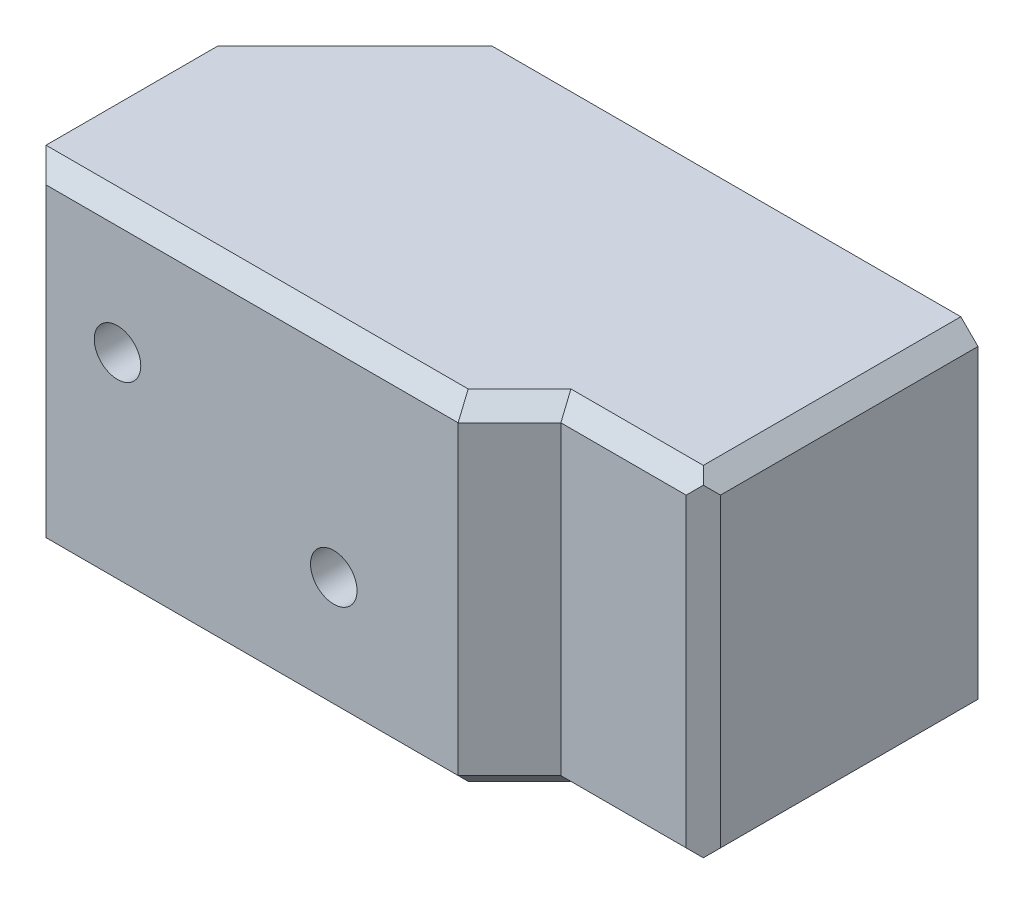
SolidWorks part; units mm, degrees
material "PET"
ref_plane "Front Plane" through (0, 0, 0) normal (0, 0, 1) x (1, 0, 0)
ref_plane "Top Plane" through (0, 0, 0) normal (0, 1, 0) x (1, 0, 0)
ref_plane "Right Plane" through (0, 0, 0) normal (1, 0, 0) x (0, 0, -1)
sketch "Sketch1" plane through (0, 0, 0) normal (0, 0, 1) x (1, 0, 0)
  line L0 (37.2, 18.6106) -> (1.8, 18.6106) construction
  line L1 (1.8, -1.3894) -> (56.25, -1.3894)
  line L2 (1.8, -1.3894) -> (1.8, 18.6106)
  line L3 (1.8, 18.6106) -> (56.25, 18.6106)
  line L4 (56.25, -1.3894) -> (56.25, 18.6106)
  line L5 (37.2, 18.6106) -> (37.2, -1.3894) construction
  point P5 (1.8, 18.6106)
  dimension "D1" = 19.05
extrude "Boss-Extrude1" add sketch "Sketch1" along normal blind 3.175
sketch "Sketch2" plane through (56.25, 0, 0) normal (1, 0, 0) x (0, 0, -1)
  line L0 (0, 18.6106) -> (0, 21.1506)
  line L1 (0, 21.1506) -> (22.225, 21.1506)
  line L6 (0, 8.6106) -> (-3.175, 8.6106) construction
  line L7 (0, -1.3894) -> (0, 18.6106) construction
  line L8 (-3.175, -1.3894) -> (-3.175, 18.6106) construction
  line L9 (-3.175, 18.6106) -> (-3.175, 24.3256)
  line L10 (-3.175, 24.3256) -> (22.225, 24.3256)
  line L11 (0, 18.6106) -> (-3.175, 18.6106)
  line L12 (22.225, 21.1506) -> (22.225, 24.3256)
  line L13 (22.225, -3.9294) -> (22.225, -7.1044)
  line L14 (0, -1.3894) -> (-3.175, -1.3894)
  line L15 (-3.175, -7.1044) -> (22.225, -7.1044)
  line L16 (-3.175, -1.3894) -> (-3.175, -7.1044)
  line L17 (0, -3.9294) -> (22.225, -3.9294)
  line L18 (0, -1.3894) -> (0, -3.9294)
  dimension "D1" = 22.225
  dimension "D2" = 2.54
  dimension "D3" = 3.175
extrude "Boss-Extrude2" add sketch "Sketch2" against normal up to surface (54.45 mm away) up to face at (1.8, 8.6106, 1.5875)
sketch "Sketch3" plane through (56.25, 0, 0) normal (1, 0, 0) x (0, 0, -1)
  line L1 (-3.175, 24.3256) -> (22.225, 24.3256)
  line L2 (-3.175, 24.3256) -> (-3.175, -7.1044)
  line L3 (-3.175, -7.1044) -> (22.225, -7.1044)
  line L4 (22.225, 24.3256) -> (22.225, -7.1044)
extrude "Boss-Extrude3" add sketch "Sketch3" along normal blind 3.175
chamfer "Chamfer1" distance 1.5875 angle 45 8 edges at (59.425, 24.3256, -9.525) (59.425, 8.6106, 3.175) (59.425, -7.1044, -9.525) (29.025, 21.1506, 0) (29.025, -3.9294, 0) (56.25, 21.1506, -11.1125) (56.25, 8.6106, 0) (56.25, -3.9294, -11.1125)
chamfer "Chamfer2" distance 12.7 angle 45 2 edges at (1.8, 22.7381, -22.225) (1.8, -5.5169, -22.225)
sketch "Sketch5" plane through (0, 0, 3.175) normal (0, 0, 1) x (1, 0, 0)
  line L0 (1.8, -7.1044) -> (57.8375, -7.1044) construction
  line L1 (1.8, 24.3256) -> (33.55, 24.3256)
  line L2 (1.8, 24.3256) -> (1.8, -7.1044)
  line L3 (1.8, -7.1044) -> (33.55, -7.1044)
  line L4 (33.55, 24.3256) -> (33.55, -7.1044)
  dimension "D1" = 31.75
extrude "Boss-Extrude5" add sketch "Sketch5" along normal offset from surface (4.7498 mm away) 7.9248 up to face at (28.2313, 8.6106, 0)
chamfer "Chamfer3" distance 12.7 angle 45 1 edges at (33.55, 8.6106, 3.175)
chamfer "Chamfer4" distance 1.5875 angle 45 7 edges at (52.0438, -7.1044, 3.175) (43.8751, -7.1044, 5.5499) (21.6501, -7.1044, 7.9248) (1.8, 8.6106, 7.9248) (21.6501, 24.3256, 7.9248) (43.8751, 24.3256, 5.5499) (52.0438, 24.3256, 3.175)
hole_wizard "#6 Clearance Hole1" positions "Sketch6" profile "Sketch7" hole size "#6" standard "ANSI Inch" end condition up to next
sketch "Sketch6" plane through (0, 0, 7.9248) normal (0, 0, 1) x (1, 0, 0)
  point P1 (10, 12.6106)
  point P4 (30, 4.6106)
sketch "Sketch7" plane through (10, 12.6106, 7.9248) normal (1, 0, 0) x (0, -1, 0)
  line L0 (0, 0) -> (0, 7.9248)
  line L1 (0, 7.9248) -> (2.1526, 7.9248)
  line L2 (2.1526, 7.9248) -> (2.1526, 0)
  line L5 (2.1526, 0) -> (0, 0)
  line L11 (0, -6.35) -> (0, 107.95) construction
  dimension "Thru Hole Dia." = 4.3053
  dimension "Thru Hole Depth" = 7.9248
